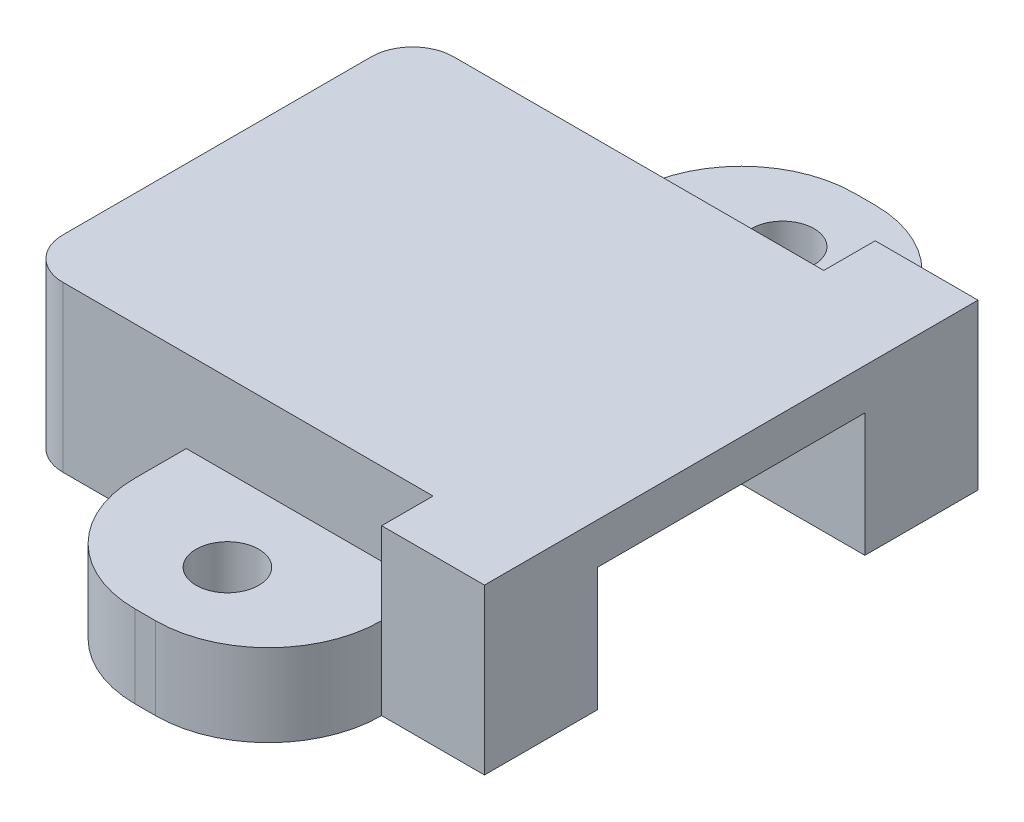
SolidWorks part; units mm, degrees
ref_plane "Front Plane" through (0, 0, 0) normal (0, 0, 1) x (1, 0, 0)
ref_plane "Top Plane" through (0, 0, 0) normal (0, 1, 0) x (1, 0, 0)
ref_plane "Right Plane" through (0, 0, 0) normal (1, 0, 0) x (0, 0, -1)
sketch "Sketch1" plane through (0, 0, 0) normal (0, 1, 0) x (1, 0, 0)
  line L0 (-1, -3) -> (23, -3)
  line L1 (0, 0) -> (22, 0)
  line L2 (0, 0) -> (0, 13)
  line L3 (0, 13) -> (22, 13)
  line L4 (22, 0) -> (22, 13)
  line L5 (25, -1) -> (25, 14)
  line L6 (-1, 16) -> (23, 16)
  line L7 (-3, -1) -> (-3, 14)
  line L8 (-3, -3) -> (25, -3) construction
  line L9 (25, -3) -> (25, 16) construction
  line L10 (-3, 16) -> (25, 16) construction
  line L11 (-3, -3) -> (-3, 16) construction
  line L12 (25, 14) -> (25, 16)
  line L13 (25, 16) -> (23, 16)
  line L14 (25, -1) -> (25, -3)
  line L15 (25, -3) -> (23, -3)
  arc A2 (-1, 16) -> (-3, 14) centre (-1, 14) ccw
  arc A3 (-1, -3) -> (-3, -1) centre (-1, -1) cw
  dimension "D1" = 22
  dimension "D2" = 13
  dimension "D3" = 3
extrude "Boss-Extrude1" add sketch "Sketch1" along normal blind 6
sketch "Sketch2" plane through (0, 6, 0) normal (0, 1, 0) x (1, 0, 0)
  line L0 (25, 14) -> (25, -1)
  line L1 (23, -3) -> (-1, -3)
  line L2 (-3, -1) -> (-3, 14)
  line L3 (-1, 16) -> (23, 16)
  line L4 (25, 16) -> (-1, 16) construction
  line L5 (23, 16) -> (25, 16)
  line L6 (25, -3) -> (25, 16) construction
  line L7 (25, 16) -> (25, 14)
  line L8 (25, -1) -> (25, -3)
  line L9 (-1, -3) -> (25, -3) construction
  line L10 (25, -3) -> (23, -3)
  arc A1 (-1, -3) -> (-3, -1) centre (-1, -1) cw
  arc A2 (-3, 14) -> (-1, 16) centre (-1, 14) cw
extrude "Boss-Extrude2" add sketch "Sketch2" along normal blind 2
sketch "Sketch3" plane through (0, 0, 0) normal (0, -1, 0) x (1, 0, 0)
  line L0 (-1, 3) -> (25, 3) construction
  line L1 (5, 3) -> (17, 3)
  line L2 (5, 3) -> (5, 5.5)
  line L3 (10.5, 11) -> (11.5, 11)
  line L4 (17, 3) -> (17, 5.5)
  line L5 (25, -16) -> (-1, -16) construction
  line L6 (17, -16) -> (5, -16)
  line L7 (17, -16) -> (17, -18.5)
  line L8 (11.5, -24) -> (10.5, -24)
  line L9 (5, -16) -> (5, -18.5)
  line L10 (25, 3) -> (25, -16) construction
  line L11 (-3, -14) -> (-3, 1) construction
  arc A0 (17, -18.5) -> (11.5, -24) centre (11.5, -18.5) cw
  arc A1 (10.5, -24) -> (5, -18.5) centre (10.5, -18.5) cw
  arc A2 (5, 5.5) -> (10.5, 11) centre (10.5, 5.5) cw
  arc A3 (11.5, 11) -> (17, 5.5) centre (11.5, 5.5) cw
  point P16 (17, -17.25)
  point P19 (17, -24)
  point P26 (17, 11)
  dimension "D7" = 5.5
  dimension "D1" = 8
  dimension "D2" = 8
  dimension "D3" = 8
  dimension "D4" = 8
  dimension "D5" = 8
  dimension "D6" = 8
extrude "Boss-Extrude3" add sketch "Sketch3" against normal up to surface (8 mm away) up to face at (6.8619, 8, -6.5)
sketch "Sketch4" plane through (0, 0, 0) normal (0, -1, 0) x (-1, 0, 0)
  line L0 (-17, 18.5) -> (-17, 16) construction
  line L2 (-10.5, 24) -> (-11.5, 24) construction
  line L3 (-11.5, -11) -> (-10.5, -11) construction
  line L4 (-5, -5.5) -> (-5, -3) construction
  circle A0 centre (-11, 20) radius 1.525
  circle A1 centre (-11, -7) radius 1.524
  point P9 (-11, 24)
  dimension "D1" = 3.048
  dimension "D2" = 3.05
  dimension "D3" = 6
  dimension "D4" = 4
  dimension "D5" = 4
  dimension "D6" = 6
extrude "Cut-Extrude1" cut sketch "Sketch4" against normal through all
sketch "Sketch5" plane through (25, 0, 0) normal (1, 0, 0) x (0, 0, -1)
  line L0 (-3, 0) -> (16, 0) construction
  line L1 (11, 0) -> (2, 0)
  line L2 (11, 0) -> (11, 4.0887)
  line L3 (11, 4.0887) -> (2, 4.0887)
  line L4 (2, 0) -> (2, 4.0887)
  line L5 (16, 8) -> (16, 0) construction
  line L6 (-3, 8) -> (-3, 0) construction
  dimension "D1" = 5
  dimension "D2" = 5
extrude "Cut-Extrude2" cut sketch "Sketch5" against normal through all
fillet "Fillet1" radius 2 4 edges at (-1.5, 4.0887, -2) (-1.5, 4.0887, -11) (23.5, 4.0887, -11) (23.5, 4.0887, -2)
sketch "Sketch6" plane through (0, 8, 0) normal (0, 1, 0) x (1, 0, 0)
  line L0 (-1, -3) -> (5, -3) construction
  line L1 (17, 16) -> (5, 16)
  line L2 (17, 16) -> (17, 29.009)
  line L3 (17, 29.009) -> (5, 29.009)
  line L4 (5, 16) -> (5, 29.009)
  line L5 (19.0682, -16.009) -> (3.2299, -16.009)
  line L6 (19.0682, -16.009) -> (19.0682, -3)
  line L7 (19.0682, -3) -> (3.2299, -3)
  line L8 (3.2299, -16.009) -> (3.2299, -3)
extrude "Cut-Extrude3" cut sketch "Sketch6" against normal blind 4
sketch "Sketch7" plane through (25, 0, 0) normal (1, 0, 0) x (0, 0, -1)
  line L0 (18.5, 4) -> (18.5, 0) construction
  line L1 (16, 8) -> (18.5, 8)
  line L2 (16, 8) -> (16, 0)
  line L3 (16, 0) -> (18.5, 0)
  line L4 (18.5, 8) -> (18.5, 0)
  line L5 (-3, 8) -> (-5.5, 8)
  line L6 (-3, 8) -> (-3, 0)
  line L7 (-3, 0) -> (-5.5, 0)
  line L8 (-5.5, 8) -> (-5.5, 0)
  line L9 (18.5, 0) -> (16, 0) construction
  line L10 (-5.5, 4) -> (-5.5, 0) construction
  line L11 (-3, 0) -> (-5.5, 0) construction
extrude "Boss-Extrude5" add sketch "Sketch7" against normal blind 3
fillet "Fillet3" radius 2.5 1 edges at (22, 4, -16)
fillet "Fillet4" radius 2.5 1 edges at (22, 4, 3)
sketch "Sketch9" plane through (25, 0, 0) normal (1, 0, 0) x (0, 0, -1)
  line L1 (18.5, 8) -> (-5.5, 8)
  line L2 (18.5, 8) -> (18.5, 0)
  line L3 (18.5, 0) -> (-5.5, 0)
  line L4 (-5.5, 8) -> (-5.5, 0)
extrude "Cut-Extrude5" cut sketch "Sketch9" against normal blind 3
sketch "Sketch10" plane through (0, 8, 0) normal (0, 1, 0) x (1, 0, 0)
  line L1 (17, 16) -> (22, 16)
  line L2 (17, 16) -> (17, 18.5)
  line L3 (17, 18.5) -> (22, 18.5)
  line L4 (22, 16) -> (22, 18.5)
  line L5 (17, -3) -> (22, -3)
  line L6 (17, -3) -> (17, -5.5)
  line L7 (17, -5.5) -> (22, -5.5)
  line L8 (22, -3) -> (22, -5.5)
extrude "Boss-Extrude6" add sketch "Sketch10" against normal up to surface (8 mm away) up to face at (8.7574, 0, 3.5482)
